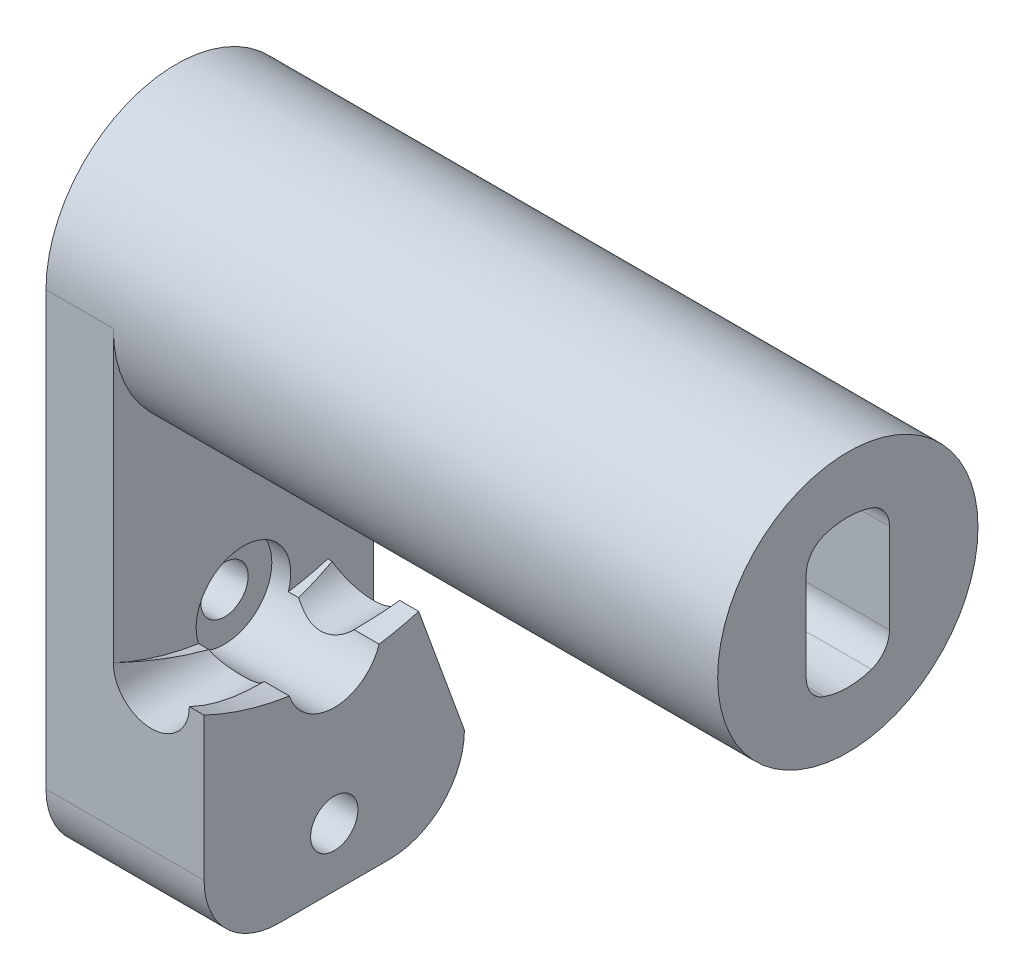
SolidWorks part; units mm, degrees
material "ABS"
ref_plane "Front Plane" through (0, 0, 0) normal (1, 0, 0) x (0, 1, 0)
ref_plane "Top Plane" through (0, 0, 0) normal (0, 0, 1) x (0, 1, 0)
ref_plane "Right Plane" through (0, 0, 0) normal (0, 1, 0) x (-1, 0, 0)
sketch "Sketch1" plane through (0, 0, 0) normal (1, 0, 0) x (0, 1, 0)
  circle A2 centre (0, 0) radius 8.7376
  dimension "D3" = 17.4752
extrude "Boss-Extrude1" add sketch "Sketch1" along normal blind 45.085 contours A2 region at (0, 0, 0)
sketch "Sketch10" plane through (0, 0, 0) normal (-1, 0, 0) x (0, -1, 0)
  line L0 (0, 8.7376) -> (34.036, 8.7376)
  line L2 (34.036, 8.7376) -> (34.036, -8.7376)
  line L3 (34.036, -8.7376) -> (0, -8.7376)
  circle A0 centre (0, 0) radius 8.7376 construction
  arc A2 (0, 8.7376) -> (0, -8.7376) centre (0, 0) cw
  dimension "D1" = 34.036
extrude "Boss-Extrude3" add sketch "Sketch10" against normal blind 4.516 contours L0 A2 L3 L2 region at (0, -20.3793, 0)
fillet "Fillet2" radius 5 2 edges at (2.258, -34.036, 8.7376) (2.258, -34.036, -8.7376)
sketch "Sketch14" [suppressed] plane through (0, 0, 0) normal (-1, 0, 0) x (0, 0, 1)
  line L0 (0.5115, -3.4237) -> (0.3944, -4.0089)
  line L1 (0, 0) -> (0, -4.064) construction
  line L2 (0, 0) -> (0.5606, -3.4335) construction
  line L3 (0.6039, -3.4087) -> (0.9011, -3.9262)
  line L4 (-0.6903, -3.3922) -> (-1.0005, -3.9021)
  line L5 (-0.5983, -3.4096) -> (-0.4961, -3.9976)
  line L6 (-1.8089, -2.9515) -> (-2.2748, -3.3245)
  line L7 (-1.7284, -2.9994) -> (-1.8334, -3.5869)
  line L8 (-2.7093, -2.1549) -> (-3.2746, -2.346)
  line L9 (-2.65, -2.2273) -> (-2.9496, -2.7435)
  line L10 (-3.2829, -1.0983) -> (-3.8795, -1.0846)
  line L11 (-3.252, -1.1867) -> (-3.7101, -1.5692)
  line L12 (-3.4605, 0.0907) -> (-4.0165, 0.3077)
  line L13 (-3.4617, -0.0029) -> (-4.023, -0.2057)
  line L14 (-3.2208, 1.2689) -> (-3.669, 1.6629)
  line L15 (-3.2539, 1.1813) -> (-3.8507, 1.1827)
  line L16 (-2.5926, 2.2939) -> (-2.879, 2.8175)
  line L17 (-2.6537, 2.223) -> (-3.214, 2.4284)
  line L18 (-1.6517, 3.0423) -> (-1.7417, 3.6323)
  line L19 (-1.7333, 2.9965) -> (-2.1896, 3.3812)
  line L20 (-0.5115, 3.4237) -> (-0.3944, 4.0089)
  line L21 (-0.6039, 3.4087) -> (-0.9011, 3.9262)
  line L22 (0.6903, 3.3922) -> (1.0005, 3.9021)
  line L23 (0.5983, 3.4096) -> (0.4961, 3.9976)
  line L24 (1.8089, 2.9515) -> (2.2748, 3.3245)
  line L25 (1.7284, 2.9994) -> (1.8334, 3.5869)
  line L26 (2.7093, 2.1549) -> (3.2746, 2.346)
  line L27 (2.65, 2.2273) -> (2.9496, 2.7435)
  line L28 (3.2829, 1.0983) -> (3.8795, 1.0846)
  line L29 (3.252, 1.1867) -> (3.7101, 1.5692)
  line L30 (3.4605, -0.0907) -> (4.0165, -0.3077)
  line L31 (3.4617, 0.0029) -> (4.023, 0.2057)
  line L32 (3.2208, -1.2689) -> (3.669, -1.6629)
  line L33 (3.2539, -1.1813) -> (3.8507, -1.1827)
  line L34 (2.5926, -2.2939) -> (2.879, -2.8175)
  line L35 (2.6537, -2.223) -> (3.214, -2.4284)
  line L36 (1.6517, -3.0423) -> (1.7417, -3.6323)
  line L37 (1.7333, -2.9965) -> (2.1896, -3.3812)
  line L38 (-0.1032, -4.0627) -> (0, -4.064)
  line L39 (-1.4865, -3.7824) -> (-1.39, -3.8189)
  line L40 (-2.6905, -3.0459) -> (-2.6123, -3.1132)
  line L41 (-3.5195, -2.032) -> (-3.57, -1.942)
  line L42 (-4.0023, -0.7057) -> (-4.0189, -0.6039)
  line L43 (-4.0023, 0.7057) -> (-3.9831, 0.8071)
  line L44 (-3.5195, 2.032) -> (-3.4668, 2.1207)
  line L45 (-2.6123, 3.1132) -> (-2.5324, 3.1785)
  line L46 (-1.39, 3.8189) -> (-1.2926, 3.853)
  line L47 (0, 4.064) -> (0.1032, 4.0627)
  line L48 (1.39, 3.8189) -> (1.4865, 3.7824)
  line L49 (2.6123, 3.1132) -> (2.6905, 3.0459)
  line L50 (3.5195, 2.032) -> (3.57, 1.942)
  line L51 (4.0023, 0.7057) -> (4.0189, 0.6039)
  line L52 (4.0023, -0.7057) -> (3.9831, -0.8071)
  line L53 (3.5195, -2.032) -> (3.4668, -2.1207)
  line L54 (2.6123, -3.1132) -> (2.5324, -3.1785)
  line L55 (1.39, -3.8189) -> (1.2926, -3.853)
  arc A0 (0.3497, -4.0489) -> (0, -4.064) centre (0, 0) cw
  arc A1 (0.3497, -4.0489) -> (0.3944, -4.0089) centre (0.3454, -3.9991) ccw
  arc A2 (0.5115, -3.4237) -> (0.6039, -3.4087) centre (0.5606, -3.4335) cw
  arc A3 (0.4203, -4.0631) -> (0.3944, -4.0089) centre (0.4434, -4.0187) cw
  arc A4 (0.4203, -4.0631) -> (0.7372, -4.2116) centre (2.3016, -0.4608) ccw
  arc A6 (0.9562, -3.9499) -> (0.9011, -3.9262) centre (0.9445, -3.9013) cw
  arc A7 (0.9562, -3.9499) -> (1.2926, -3.853) centre (0, 0) ccw
  arc A8 (-1.0562, -3.9243) -> (-1.39, -3.8189) centre (0, 0) cw
  arc A9 (-1.0562, -3.9243) -> (-1.0005, -3.9021) centre (-1.0432, -3.8761) ccw
  arc A10 (-0.6903, -3.3922) -> (-0.5983, -3.4096) centre (-0.6476, -3.4182) cw
  arc A11 (-0.4524, -4.0387) -> (-0.4961, -3.9976) centre (-0.4468, -3.9891) cw
  arc A12 (-0.4524, -4.0387) -> (-0.1032, -4.0627) centre (0, 0) ccw
  arc A13 (-2.3347, -3.3264) -> (-2.6123, -3.1132) centre (0, 0) cw
  arc A14 (-2.3347, -3.3264) -> (-2.2748, -3.3245) centre (-2.306, -3.2855) ccw
  arc A15 (-1.8089, -2.9515) -> (-1.7284, -2.9994) centre (-1.7776, -2.9906) cw
  arc A16 (-1.8064, -3.6405) -> (-1.8334, -3.5869) centre (-1.7842, -3.5957) cw
  arc A17 (-1.8064, -3.6405) -> (-1.4865, -3.7824) centre (0, 0) ccw
  arc A18 (-3.3316, -2.3273) -> (-3.5195, -2.032) centre (0, 0) cw
  arc A19 (-3.3316, -2.3273) -> (-3.2746, -2.346) centre (-3.2906, -2.2987) ccw
  arc A20 (-2.7093, -2.1549) -> (-2.65, -2.2273) centre (-2.6933, -2.2022) cw
  arc A21 (-2.9426, -2.8031) -> (-2.9496, -2.7435) centre (-2.9064, -2.7686) cw
  arc A22 (-2.9426, -2.8031) -> (-2.6905, -3.0459) centre (0, 0) ccw
  arc A23 (-3.9267, -1.0475) -> (-4.0023, -0.7057) centre (0, 0) cw
  arc A24 (-3.9267, -1.0475) -> (-3.8795, -1.0846) centre (-3.8784, -1.0346) ccw
  arc A25 (-3.2829, -1.0983) -> (-3.252, -1.1867) centre (-3.284, -1.1483) cw
  arc A26 (-3.7238, -1.6276) -> (-3.7101, -1.5692) centre (-3.678, -1.6076) cw
  arc A27 (-3.7238, -1.6276) -> (-3.57, -1.942) centre (0, 0) ccw
  arc A28 (-4.0481, 0.3587) -> (-4.0023, 0.7057) centre (0, 0) cw
  arc A29 (-4.0481, 0.3587) -> (-4.0165, 0.3077) centre (-3.9983, 0.3543) ccw
  arc A30 (-3.4605, 0.0907) -> (-3.4617, -0.0029) centre (-3.4787, 0.0442) cw
  arc A31 (-4.0559, -0.2558) -> (-4.023, -0.2057) centre (-4.006, -0.2527) cw
  arc A32 (-4.0559, -0.2558) -> (-4.0189, -0.6039) centre (0, 0) ccw
  arc A33 (-3.6813, 1.7216) -> (-3.5195, 2.032) centre (0, 0) cw
  arc A34 (-3.6813, 1.7216) -> (-3.669, 1.6629) centre (-3.636, 1.7005) ccw
  arc A35 (-3.2208, 1.2689) -> (-3.2539, 1.1813) centre (-3.2538, 1.2313) cw
  arc A36 (-3.8988, 1.1468) -> (-3.8507, 1.1827) centre (-3.8509, 1.1327) cw
  arc A37 (-3.8988, 1.1468) -> (-3.9831, 0.8071) centre (0, 0) ccw
  arc A38 (-2.8705, 2.8769) -> (-2.6123, 3.1132) centre (0, 0) cw
  arc A39 (-2.8705, 2.8769) -> (-2.879, 2.8175) centre (-2.8352, 2.8415) ccw
  arc A40 (-2.5926, 2.2939) -> (-2.6537, 2.223) centre (-2.6365, 2.2699) cw
  arc A41 (-3.2715, 2.4111) -> (-3.214, 2.4284) centre (-3.2312, 2.3815) cw
  arc A42 (-3.2715, 2.4111) -> (-3.4668, 2.1207) centre (0, 0) ccw
  arc A43 (-1.7134, 3.6852) -> (-1.39, 3.8189) centre (0, 0) cw
  arc A44 (-1.7134, 3.6852) -> (-1.7417, 3.6323) centre (-1.6923, 3.6398) ccw
  arc A45 (-1.6517, 3.0423) -> (-1.7333, 2.9965) centre (-1.7011, 3.0348) cw
  arc A46 (-2.2495, 3.3846) -> (-2.1896, 3.3812) centre (-2.2218, 3.343) cw
  arc A47 (-2.2495, 3.3846) -> (-2.5324, 3.1785) centre (0, 0) ccw
  arc A48 (-0.3497, 4.0489) -> (0, 4.064) centre (0, 0) cw
  arc A49 (-0.3497, 4.0489) -> (-0.3944, 4.0089) centre (-0.3454, 3.9991) ccw
  arc A50 (-0.5115, 3.4237) -> (-0.6039, 3.4087) centre (-0.5606, 3.4335) cw
  arc A51 (-0.9562, 3.9499) -> (-0.9011, 3.9262) centre (-0.9445, 3.9013) cw
  arc A52 (-0.9562, 3.9499) -> (-1.2926, 3.853) centre (0, 0) ccw
  arc A53 (1.0562, 3.9243) -> (1.39, 3.8189) centre (0, 0) cw
  arc A54 (1.0562, 3.9243) -> (1.0005, 3.9021) centre (1.0432, 3.8761) ccw
  arc A55 (0.6903, 3.3922) -> (0.5983, 3.4096) centre (0.6476, 3.4182) cw
  arc A56 (0.4524, 4.0387) -> (0.4961, 3.9976) centre (0.4468, 3.9891) cw
  arc A57 (0.4524, 4.0387) -> (0.1032, 4.0627) centre (0, 0) ccw
  arc A58 (2.3347, 3.3264) -> (2.6123, 3.1132) centre (0, 0) cw
  arc A59 (2.3347, 3.3264) -> (2.2748, 3.3245) centre (2.306, 3.2855) ccw
  arc A60 (1.8089, 2.9515) -> (1.7284, 2.9994) centre (1.7776, 2.9906) cw
  arc A61 (1.8064, 3.6405) -> (1.8334, 3.5869) centre (1.7842, 3.5957) cw
  arc A62 (1.8064, 3.6405) -> (1.4865, 3.7824) centre (0, 0) ccw
  arc A63 (3.3316, 2.3273) -> (3.5195, 2.032) centre (0, 0) cw
  arc A64 (3.3316, 2.3273) -> (3.2746, 2.346) centre (3.2906, 2.2987) ccw
  arc A65 (2.7093, 2.1549) -> (2.65, 2.2273) centre (2.6933, 2.2022) cw
  arc A66 (2.9426, 2.8031) -> (2.9496, 2.7435) centre (2.9064, 2.7686) cw
  arc A67 (2.9426, 2.8031) -> (2.6905, 3.0459) centre (0, 0) ccw
  arc A68 (3.9267, 1.0475) -> (4.0023, 0.7057) centre (0, 0) cw
  arc A69 (3.9267, 1.0475) -> (3.8795, 1.0846) centre (3.8784, 1.0346) ccw
  arc A70 (3.2829, 1.0983) -> (3.252, 1.1867) centre (3.284, 1.1483) cw
  arc A71 (3.7238, 1.6276) -> (3.7101, 1.5692) centre (3.678, 1.6076) cw
  arc A72 (3.7238, 1.6276) -> (3.57, 1.942) centre (0, 0) ccw
  arc A73 (4.0481, -0.3587) -> (4.0023, -0.7057) centre (0, 0) cw
  arc A74 (4.0481, -0.3587) -> (4.0165, -0.3077) centre (3.9983, -0.3543) ccw
  arc A75 (3.4605, -0.0907) -> (3.4617, 0.0029) centre (3.4787, -0.0442) cw
  arc A76 (4.0559, 0.2558) -> (4.023, 0.2057) centre (4.006, 0.2527) cw
  arc A77 (4.0559, 0.2558) -> (4.0189, 0.6039) centre (0, 0) ccw
  arc A78 (3.6813, -1.7216) -> (3.5195, -2.032) centre (0, 0) cw
  arc A79 (3.6813, -1.7216) -> (3.669, -1.6629) centre (3.636, -1.7005) ccw
  arc A80 (3.2208, -1.2689) -> (3.2539, -1.1813) centre (3.2538, -1.2313) cw
  arc A81 (3.8988, -1.1468) -> (3.8507, -1.1827) centre (3.8509, -1.1327) cw
  arc A82 (3.8988, -1.1468) -> (3.9831, -0.8071) centre (0, 0) ccw
  arc A83 (2.8705, -2.8769) -> (2.6123, -3.1132) centre (0, 0) cw
  arc A84 (2.8705, -2.8769) -> (2.879, -2.8175) centre (2.8352, -2.8415) ccw
  arc A85 (2.5926, -2.2939) -> (2.6537, -2.223) centre (2.6365, -2.2699) cw
  arc A86 (3.2715, -2.4111) -> (3.214, -2.4284) centre (3.2312, -2.3815) cw
  arc A87 (3.2715, -2.4111) -> (3.4668, -2.1207) centre (0, 0) ccw
  arc A88 (1.7134, -3.6852) -> (1.39, -3.8189) centre (0, 0) cw
  arc A89 (1.7134, -3.6852) -> (1.7417, -3.6323) centre (1.6923, -3.6398) ccw
  arc A90 (1.6517, -3.0423) -> (1.7333, -2.9965) centre (1.7011, -3.0348) cw
  arc A91 (2.2495, -3.3846) -> (2.1896, -3.3812) centre (2.2218, -3.343) cw
  arc A92 (2.2495, -3.3846) -> (2.5324, -3.1785) centre (0, 0) ccw
  point P207 (0, 0)
  dimension "D1" = 4.064
  dimension "D2" = 0.05
  dimension "D3" = 0.05
  dimension "D4" = 0.04
  dimension "D5" = 18
  dimension "D6" = 0.5968
  dimension "D8" = 0.35
sketch "Sketch15" plane through (4.516, 0, 0) normal (1, 0, 0) x (0, 1, 0)
  line L1 (-29.036, 8.7376) -> (-18.796, 8.7376)
  line L2 (-18.796, 8.7376) -> (-18.796, -5.0105)
  line L3 (0, 8.7376) -> (-29.036, 8.7376) construction
  line L4 (-29.036, -8.7376) -> (-18.796, -5.0105)
  line L5 (-34.036, 3.7376) -> (-34.036, -3.7376) construction
  line L6 (-34.036, 3.7376) -> (-34.036, -3.7376)
  line L13 (0, 8.7376) -> (-29.036, 8.7376)
  line L14 (-34.036, 3.7376) -> (-34.036, -3.7376)
  line L15 (-29.036, -8.7376) -> (0, -8.7376)
  line L17 (-34.036, 3.7376) -> (-34.036, -3.7376)
  arc A0 (-29.036, 8.7376) -> (-34.036, 3.7376) centre (-29.036, 3.7376) ccw construction
  arc A1 (-34.036, -3.7376) -> (-29.036, -8.7376) centre (-29.036, -3.7376) ccw construction
  arc A2 (-29.036, 8.7376) -> (-34.036, 3.7376) centre (-29.036, 3.7376) ccw
  arc A3 (-34.036, -3.7376) -> (-29.036, -8.7376) centre (-29.036, -3.7376) ccw
  arc A7 (-29.036, 8.7376) -> (-34.036, 3.7376) centre (-29.036, 3.7376) ccw
  arc A8 (-34.036, -3.7376) -> (-29.036, -8.7376) centre (-29.036, -3.7376) ccw
  arc A9 (0, 8.7376) -> (0, -8.7376) centre (0, 0) ccw
  arc A10 (-29.036, 8.7376) -> (-34.036, 3.7376) centre (-29.036, 3.7376) ccw
  arc A11 (-34.036, -3.7376) -> (-29.036, -8.7376) centre (-29.036, -3.7376) ccw
  arc A12 (0, 8.7376) -> (0, -8.7376) centre (0, 0) ccw
  line M2 (0, 8.7376) -> (-29.036, 8.7376)
  arc M3 (-29.036, 8.7376) -> (-34.036, 3.7376) centre (-29.036, 3.7376) ccw
  line M4 (-34.036, 3.7376) -> (-34.036, -3.7376)
  arc M5 (-34.036, -3.7376) -> (-29.036, -8.7376) centre (-29.036, -3.7376) ccw
  dimension "D1" = 15.24
  dimension "D3" = 20
  dimension "D2" = 0
extrude "Boss-Extrude4" add sketch "Sketch15" along normal blind 6.096 contours M2 M3 M4 M5 region at (4.516, -26.4604, 0.6047)
sketch "Sketch21" plane through (10.612, 0, 0) normal (1, 0, 0) x (0, 1, 0)
  line L2 (-18.796, -8.7376) -> (-18.796, 8.7376)
  line L4 (-29.036, 8.7376) -> (-18.796, 8.7376) construction
  line L5 (-19.431, -8.7376) -> (-18.796, -8.7376)
  line L6 (-18.796, 8.7376) -> (-18.796, -5.0105) construction
  line L8 (-29.036, -8.7376) -> (0, -8.7376) construction
  line L14 (-18.796, -8.7376) -> (-18.796, 8.7376) construction
  line L20 (-18.796, 8.7376) -> (-29.036, 8.7376)
  arc A2 (-19.431, -8.7376) -> (-19.431, 8.7376) centre (-1.0855, 0) cw
  dimension "D4" = 20.32
  dimension "D2" = 0.635
  dimension "D3" = 0.635
extrude "Cut-Extrude8" cut sketch "Sketch21" against normal up to surface (6.096 mm away) contours A2 L2 region at (10.612, -19.8652, 0) up to face at (4.516, -15.0731, -1.0021)
sketch "Sketch22" plane through (45.085, 0, 0) normal (1, 0, 0) x (0, 1, 0)
  line L7 (-4.0897, -2.794) -> (4.0897, 2.794) construction
  line L8 (-4.0897, 2.794) -> (4.0897, -2.794) construction
  line L11 (-4.0897, -2.794) -> (4.0897, -2.794)
  line L13 (-4.0897, 2.794) -> (4.0897, 2.794)
  line L15 (-4.0897, -2.794) -> (4.0897, 2.794) construction
  line L16 (-4.0897, 2.794) -> (4.0897, -2.794) construction
  arc A3 (-4.0897, 2.794) -> (-4.0897, -2.794) centre (0, 0) ccw
  arc A4 (4.0897, -2.794) -> (4.0897, 2.794) centre (0, 0) ccw
  dimension "D2" = 9.906
  dimension "D3" = 5.588
extrude "Cut-Extrude10" cut sketch "Sketch22" against normal blind 12.192
sketch "Sketch23" plane through (0, 0, 0) normal (-1, 0, 0) x (0, 0, 1)
  line L0 (0, -33.5187) -> (0, 0) construction
  line L2 (0, -30.0897) -> (0, -20.1843) construction
  line L3 (0, -20.1843) -> (0, -10.279) construction
  line L6 (-3.7376, -33.5187) -> (3.7376, -33.5187)
  line L7 (8.2296, -29.0267) -> (8.2296, 0)
  line L8 (-8.2296, 0) -> (-8.2296, -29.0267)
  arc A6 (-8.2296, -29.0267) -> (-3.7376, -33.5187) centre (-3.7376, -29.0267) ccw
  arc A7 (3.7376, -33.5187) -> (8.2296, -29.0267) centre (3.7376, -29.0267) ccw
  arc A8 (8.2296, 0) -> (-8.2296, 0) centre (0, 0) ccw
  circle A9 centre (0, -30.0897) radius 1.5875
  circle A10 centre (0, -20.1843) radius 1.5875
  dimension "D1" = 3.175
  dimension "D3" = 4.492
  dimension "D5" = 8.2296
  dimension "D2" = 9.9054
  dimension "D4" = 29.0267
  dimension "D6" = 3.429
extrude "Cut-Extrude11" cut sketch "Sketch23" against normal through all contours A10 | A9 region at (0, -30.0897, 0) region at (0, -20.1843, 0)
sketch "Sketch24" plane through (4.516, 0, 0) normal (1, 0, 0) x (0, 1, 0)
  circle A0 centre (-20.1843, 0) radius 1.5875 construction
  circle A1 centre (-20.1843, 0) radius 1.5875
  circle A2 centre (-20.1843, 0) radius 3.175
  dimension "D1" = 6.35
extrude "Cut-Extrude12" cut sketch "Sketch24" along normal through all
extrude "Cut-Extrude13" cut sketch "Sketch24<2>" against normal blind 1.27
sketch "Sketch24<2>" plane through (4.516, 0, 0) normal (1, 0, 0) x (0, 1, 0) same geometry as "Sketch24"
fillet "Fillet11" radius 1.778 4 edges at (38.989, 4.0897, -2.794) (38.989, 4.0897, 2.794) (38.989, -4.0897, -2.794) (38.989, -4.0897, 2.794)
sketch "Sketch25" plane through (0, 0, -8.7376) normal (0, 0, -1) x (1, 0, 0)
  line L3 (4.516, 29.036) -> (4.516, 0) construction
  line L4 (4.516, 19.431) -> (10.612, 19.431) construction
  circle A0 centre (7.0687, 19.431) radius 2.5527
  dimension "D1" = 5.1054
extrude "Cut-Extrude14" cut sketch "Sketch25" against normal through all
